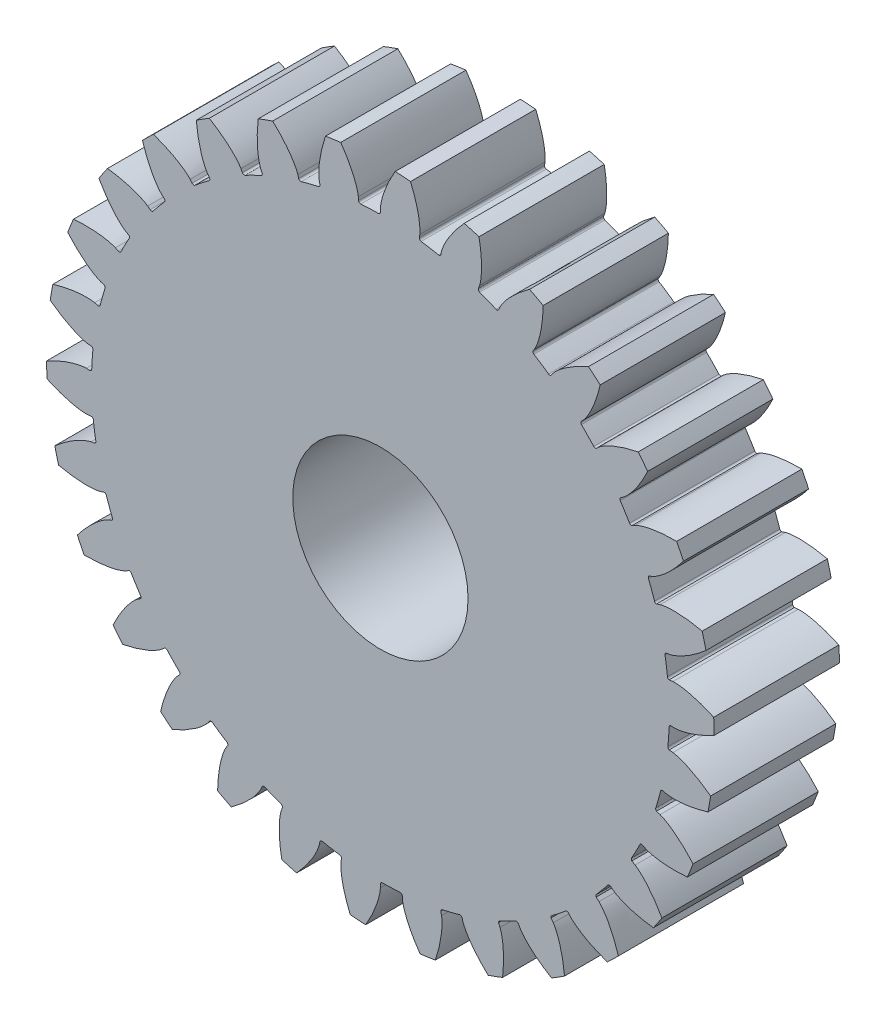
SolidWorks part; units mm, degrees
ref_plane "Alzado" through (0, 0, 0) normal (0, 0, 1) x (1, 0, 0)
ref_plane "Planta" through (0, 0, 0) normal (0, 1, 0) x (1, 0, 0)
ref_plane "Vista lateral" through (0, 0, 0) normal (1, 0, 0) x (0, 0, -1)
sketch "Croquis1" plane through (0, 0, 0) normal (0, 0, 1) x (1, 0, 0)
  line L0 (0, 0) -> (131.0885, 0) construction
  line L1 (0, 0) -> (0, 30) construction
  line L2 (0, 0) -> (12.4587, 12.4587) construction
  line L3 (12.4587, 12.4587) -> (2.6737, 22.2437) construction
  line L4 (0, 0) -> (11.3254, 13.4971) construction
  line L5 (11.3254, 13.4971) -> (1.9027, 21.4038) construction
  line L6 (0, 0) -> (10.106, 14.4328) construction
  line L7 (10.106, 14.4328) -> (1.2895, 20.6062) construction
  line L8 (0, 0) -> (8.8096, 15.2587) construction
  line L9 (8.8096, 15.2587) -> (0.8202, 19.8714) construction
  line L10 (0, 0) -> (7.4462, 15.9685) construction
  line L11 (7.4462, 15.9685) -> (0.4787, 19.2175) construction
  line L12 (0, 0) -> (6.0261, 16.5567) construction
  line L13 (6.0261, 16.5567) -> (0.2468, 18.6602) construction
  line L14 (0, 0) -> (4.5602, 17.0189) construction
  line L15 (4.5602, 17.0189) -> (0.1047, 18.2127) construction
  line L16 (0, 0) -> (3.0595, 17.3516) construction
  line L17 (3.0595, 17.3516) -> (0.0311, 17.8856) construction
  line L18 (0, 0) -> (1.5356, 17.5522) construction
  line L19 (1.5356, 17.5522) -> (0.0039, 17.6862) construction
  circle A0 centre (0, 0) radius 17.6192 construction
  circle A1 centre (0, 0) radius 17.3038 construction
  circle A2 centre (0, 0) radius 20 construction
  circle A3 centre (0, 0) radius 18.75 construction
  spline S0 degree 3 poles (0, 17.6192) (0.003, 17.7087) (0.0309, 17.9084) (0.1107, 18.2574) (0.255, 18.7048) (0.4889, 19.2621) (0.8326, 19.916) (1.5096, 20.9709) (2.1682, 21.7377) (2.6737, 22.2437) knots 0 0 0 0 0.049384 0.111113 0.197533 0.308643 0.444446 0.604939 1 1 1 1
  point P3 (87.284, 1.25)
  point P4 (102.0506, 30)
  point P5 (119.8936, 20)
  point P29 (0, 17.6192)
  dimension "Diámetro de paso (D)" = 37.5
  dimension "Diámetro de raiz" = 34.6075
  dimension "D1" = 40
  dimension "D2" = 35.2385
  dimension "Módulo (m)" = 1.25
  dimension "Número de dientes (N)" = 30
  dimension "Ángulo de presión (AP)" = 20
  dimension "D3" = 45
  dimension "D4" = 13.8381
  dimension "D5" = 40
  dimension "D6" = 12.3005
  dimension "D7" = 35
  dimension "D8" = 10.763
  dimension "D9" = 9.2254
  dimension "D10" = 30
  dimension "D11" = 25
  dimension "D12" = 7.6878
  dimension "D13" = 20
  dimension "D14" = 6.1503
  dimension "D15" = 15
  dimension "D16" = 4.6127
  dimension "D17" = 10
  dimension "D18" = 3.0751
  dimension "D19" = 5
  dimension "D20" = 1.5376
sketch "Croquis2" plane through (0, 0, 0) normal (0, 0, 1) x (1, 0, 0)
  line L0 (56.3227, 9.5882) -> (76.5884, 9.5882) construction
  line L1 (0, 17.3911) -> (0, 17.6192)
  line L2 (0, 0) -> (0.3802, 25.5087) construction
  line L3 (0, 0) -> (3.1082, 25.8589) construction
  line L4 (0, 0) -> (32.6464, 0) construction
  line L5 (0, 0) -> (131.0885, 0) construction
  line L6 (0, 0) -> (1.6991, 25.221) construction
  line L7 (2.3325, 17.2754) -> (2.3632, 17.46)
  line L8 (57.5292, -20.4598) -> (78.7754, -20.4598) construction
  circle A0 centre (0, 0) radius 17.3038 construction
  circle A1 centre (0, 0) radius 20 construction
  arc A2 (-0.1185, 17.3033) -> (2.4382, 17.1311) centre (0, 0) ccw
  arc A3 (1.8037, 19.9185) -> (0.8841, 19.9804) centre (0, 0) ccw
  circle A4 centre (0, 0) radius 18.75 construction
  circle A5 centre (0, 0) radius 5.25
  arc A6 (2.3325, 17.2754) -> (2.4382, 17.1311) centre (2.4558, 17.2549) ccw
  arc A7 (0, 17.3911) -> (-0.1185, 17.3033) centre (-0.1193, 17.4283) cw
  spline S0 degree 3 poles (3999.154, -11.1559) (22.4729, -2.4419) (-1.6764, 10.4482) (0.1107, 18.2574) (0.255, 18.7048) (0.4889, 19.2621) (0.8326, 19.916) (24.6889, 57.0873) (266.2192, -59.859) (-3996.4932, 54.198) knots -4.222676 -4.222676 -4.222676 -4.222676 0.049384 0.111113 0.197533 0.308643 0.444446 0.604939 24.668661 24.668661 24.668661 24.668661 only from (0, 17.6192) to (2.6737, 22.2437) construction
  spline S1 degree 3 poles (0, 17.6192) (0.003, 17.7087) (0.0309, 17.9084) (0.1107, 18.2574) (0.255, 18.7048) (0.4889, 19.2621) (0.7168, 19.6957) (0.8626, 19.9442) (0.8841, 19.9804) knots 0 0 0 0 0.049384 0.111113 0.197533 0.308643 0.444446 0.467706 0.467706 0.467706 0.467706
  spline S2 degree 3 poles (2.3632, 17.46) (2.3722, 17.5491) (2.3714, 17.7508) (2.339, 18.1073) (2.2561, 18.57) (2.0991, 19.1536) (1.9314, 19.6139) (1.8202, 19.8797) (1.8037, 19.9185) knots 0 0 0 0 0.049384 0.111113 0.197533 0.308643 0.444446 0.467706 0.467706 0.467706 0.467706
  point P8 (0.2795, 18.7479)
  point P13 (28.0519, 1.9635)
  point P22 (68.2533, 14.5882)
  point P25 (68.2533, 9.5402)
  dimension "Diámetro del cubo" = 10.5
  dimension "Redondeo" = 0.125
  dimension "Espesor del diente (T)" = 1.9635
  dimension "D1" = 6
  dimension "D2" = 3
  dimension "Espesor del engrane" = 5
  dimension "dientes" = 30
extrude "Saliente-Extruir1" add sketch "Croquis2" along normal blind 7.5
pattern_circular "MatrizC6" count 30 over 360 about axis through (0, 0, 7.5) along (0, 0, -1) of "Saliente-Extruir1"
equation "\"Diámetro de paso (D)@Croquis1\"=\"Módulo (m)@Croquis1\"*\"Número de dientes (N)@Croquis1\""
equation "\"Diámetro de raiz@Croquis1\"=(\"Diámetro de paso (D)@Croquis1\")-((2.314)*(\"Módulo (m)@Croquis1\"))"
equation "\"D1@Croquis1\"=(\"Diámetro de paso (D)@Croquis1\")+((2)*(\"Módulo (m)@Croquis1\"))"
equation "\"D2@Croquis1\"=(\"Diámetro de paso (D)@Croquis1\")*(cos( \"Ángulo de presión (AP)@Croquis1\"))"
equation "\"D4@Croquis1\"=(\"D2@Croquis1\"/(2))*((\"D3@Croquis1\")*(PI)/(180))"
equation "\"D6@Croquis1\"=(\"D2@Croquis1\"/(2))*((\"D5@Croquis1\")*(PI)/(180))"
equation "\"D8@Croquis1\"=(\"D2@Croquis1\"/(2))*((\"D7@Croquis1\")*(PI)/(180))"
equation "\"D9@Croquis1\"=(\"D2@Croquis1\"/(2))*((\"D10@Croquis1\")*(PI)/(180))"
equation "\"D12@Croquis1\"=(\"D2@Croquis1\"/(2))*((\"D11@Croquis1\")*(PI)/(180))"
equation "\"D14@Croquis1\"=(\"D2@Croquis1\"/(2))*((\"D13@Croquis1\")*(PI)/(180))"
equation "\"D16@Croquis1\"=(\"D2@Croquis1\"/(2))*((\"D15@Croquis1\")*(PI)/(180))"
equation "\"D18@Croquis1\"=(\"D2@Croquis1\"/(2))*((\"D17@Croquis1\")*(PI)/(180))"
equation "\"D20@Croquis1\"=(\"D2@Croquis1\"/(2))*((\"D19@Croquis1\")*(PI)/(180))"
equation "\"Espesor del diente (T)@Croquis2\"=(1.5708)*(\"Módulo (m)@Croquis1\")"
equation "\"D1@Croquis2\"=(\"Espesor del diente (T)@Croquis2\"/(\"Diámetro de paso (D)@Croquis1\"/2))*(180/PI)"
equation "\"D2@Croquis2\"=\"D1@Croquis2\"/2"
equation "\"dientes@Croquis2\"=\"Número de dientes (N)@Croquis1\""
equation "\"Redondeo@Croquis2\"=\"Módulo (m)@Croquis1\"*(0.1)"
equation "\"D1@MatrizC6\"=\"Número de dientes (N)@Croquis1\""
